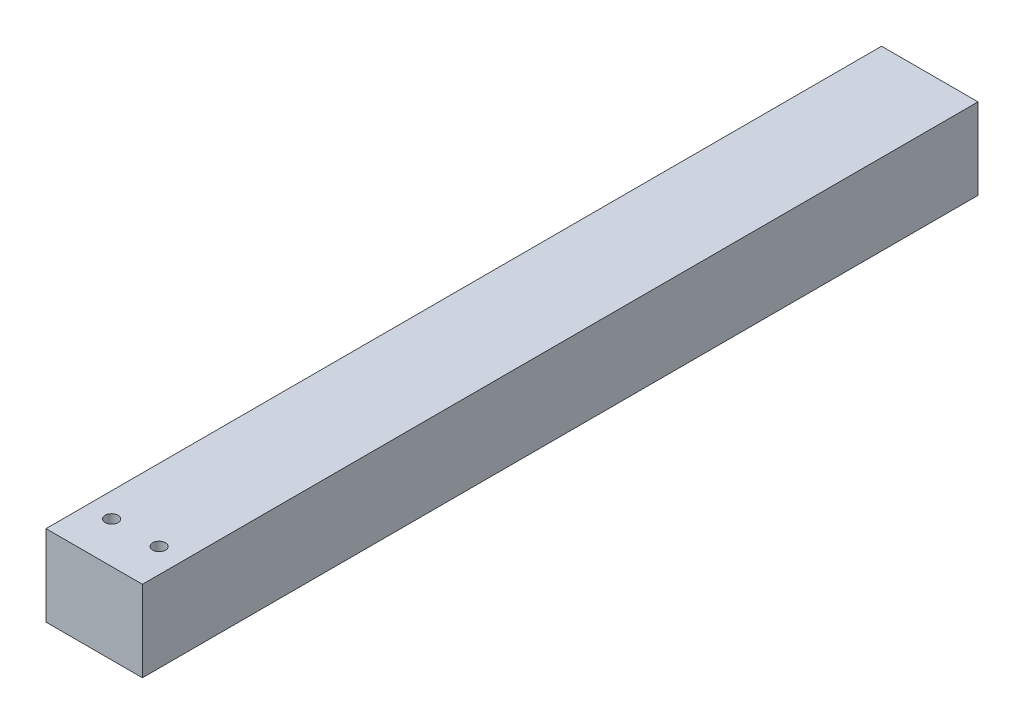
SolidWorks part; units mm, degrees
ref_plane "Front" through (0, 0, 0) normal (0, 0, 1) x (1, 0, 0)
ref_plane "Top" through (0, 0, 0) normal (0, 1, 0) x (1, 0, 0)
ref_plane "Right" through (0, 0, 0) normal (1, 0, 0) x (0, 0, -1)
sketch "Esquisse1" plane through (0, 0, 0) normal (0, 0, 1) x (1, 0, 0)
  line L1 (0, 0) -> (75, 0)
  line L2 (0, 0) -> (0, 63)
  line L3 (0, 63) -> (75, 63)
  line L4 (75, 0) -> (75, 63)
  dimension "D1" = 63
  dimension "D2" = 75
extrude "Boss.-Extru.1" add sketch "Esquisse1" along normal blind 650
sketch "Esquisse2" plane through (0, 0, 0) normal (0, -1, 0) x (1, 0, 0)
  line L0 (19, 650) -> (19, 952) construction
  line L1 (0, 650) -> (75, 650) construction
  line L2 (0, 650) -> (0, 0) construction
  line L3 (37.5, 650) -> (37.5, 952) construction
  circle A1 centre (19, 618) radius 5
  circle A2 centre (56, 618) radius 5
  dimension "D1" = 10
  dimension "D2" = 32
  dimension "D3" = 19
extrude "Enlèv. mat.-Extru.1" cut sketch "Esquisse2" against normal through all
